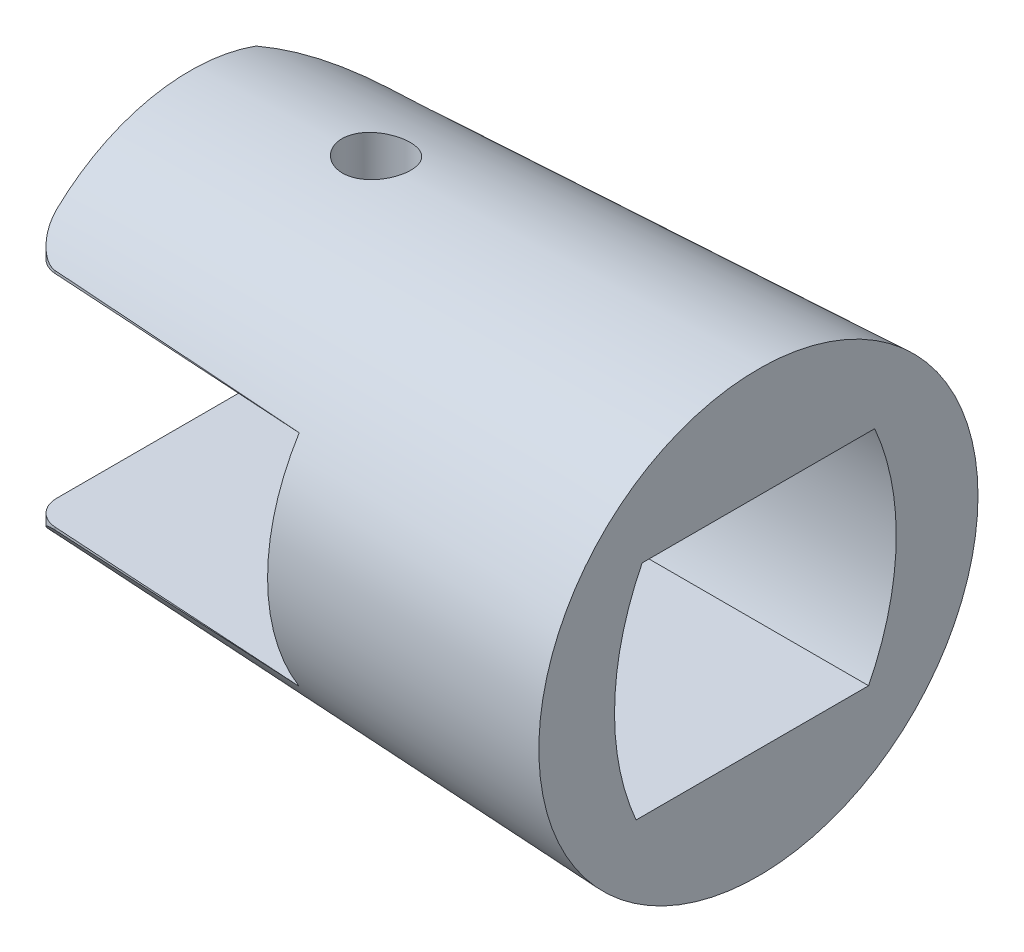
SolidWorks part; units mm, degrees
ref_plane "Ön Düzlem" through (0, 0, 0) normal (0, 0, 1) x (1, 0, 0)
ref_plane "Üst Düzlem" through (0, 0, 0) normal (0, 1, 0) x (1, 0, 0)
ref_plane "Sağ Düzlem" through (0, 0, 0) normal (1, 0, 0) x (0, 0, -1)
sketch "Sketch1" plane through (0, 0, 0) normal (1, 0, 0) x (0, 0, -1)
  circle A0 centre (0, 0) radius 8.5
  dimension "D1" = 17
sketch "Sketch3" plane through (0, 0, 0) normal (0, 1, 0) x (1, 0, 0)
  line L0 (0, 0) -> (-22, 0)
  dimension "D1" = 22
ref_plane "Plane1" through (-22, 0, 0) normal (1, 0, 0) x (0, 0, -1)
sketch "Sketch4" plane through (-22, 0, 0) normal (1, 0, 0) x (0, 0, -1)
  circle A0 centre (0, 0) radius 7.5
loft "Loft1" add profiles "Sketch4", "Sketch1" connector at (-22, 1.76, -7.2906) connector at (0, 2.119, -8.2316)
sketch "Sketch5" plane through (0, 0, 0) normal (0, 0, 1) x (1, 0, 0)
  line L0 (0, 0) -> (-10, 0) construction
  line L1 (0, 0) -> (-22, 0) construction
  line L2 (-11, 4.25) -> (-24.9848, 4.25)
  line L3 (-11, 4.25) -> (-11, -4.25)
  line L4 (-24.9848, 4.25) -> (-24.9848, -4.25)
  line L5 (-24.9848, -4.25) -> (-11, -4.25)
  line L6 (-11, -4.25) -> (-10.9931, -4.2764)
  line L7 (0, -8.5) -> (0, 8.5) construction
  dimension "D1" = 10
  dimension "D2" = 8.5
  dimension "D3" = 4.25
  dimension "D4" = 11
extrude "Cut-Extrude1" cut sketch "Sketch5" against normal blind 10 and the other way blind 10 contours L4 L5 L3 L2 region at (-17.9924, 0, 0)
sketch "Sketch7" plane through (0, 0, 0) normal (0, 1, 0) x (1, 0, 0)
  line L0 (-11, 6.7777) -> (-11, -6.7777)
  line L1 (-11, -6.7777) -> (-23.0023, -6.0429)
  line L2 (-23.0023, -6.0429) -> (-23.0231, -1.4883)
  line L3 (-11, 6.7777) -> (-16.5274, 6.6846)
  line L4 (-11, -6.7777) -> (-11, -8) construction
  line L5 (-11, 6.7777) -> (-11, 10.3705)
  line L6 (-11, 10.3705) -> (-27.9181, 10.3705)
  line L7 (-27.9181, 10.3705) -> (-27.9181, -8.5015)
  line L8 (-27.9181, -8.5015) -> (-11, -8.5015)
  line L9 (-11, -8.5015) -> (-11, -6.7777)
  arc A0 (-16.5274, 6.6846) -> (-23.0231, -1.4883) centre (-14.6815, -1.4502) ccw
  spline S0 degree 3 poles (-11, -6.7777) (-14.6668, -6.581) (-18.3335, -6.3819) (-22, -6.1796) knots 0 0 0 0 1 1 1 1 construction
  spline S1 degree 3 poles (-22, 6.1796) (-18.3335, 6.3819) (-14.6668, 6.581) (-11, 6.7777) knots 0 0 0 0 1 1 1 1 construction
  dimension "D4" = 5.5274
  dimension "D6" = 8.3417
  dimension "D1" = 12.0023
  dimension "D2" = 4.5546
  dimension "D3" = 86.496
  dimension "D5" = 89.035
extrude "Cut-Extrude2" cut sketch "Sketch7" against normal blind 10 and the other way blind 10 contours A0 L3 L5 L6 L7 L8 L9 L1 L2 region at (-13.768, 0, -6.9846)
sketch "Sketch8" plane through (0, 0, 0) normal (0, 1, 0) x (1, 0, 0)
  line L0 (-11, -8) -> (-15.3, -8) construction
  line L1 (-15.3, -8) -> (-15.3, 0.5) construction
  circle A0 centre (-15.3, 0.5) radius 1.25
  dimension "D1" = 4.3
  dimension "D2" = 8.5
extrude "Cut-Extrude3" cut sketch "Sketch8" against normal blind 10 and the other way blind 10
sketch "Sketch9" plane through (0, 0, 0) normal (1, 0, 0) x (0, 0, -1)
  line L0 (5.1446, 4.1876) -> (5.1446, -4.2327)
  line L2 (-3.4805, 4.1876) -> (-3.4805, -4.3677)
  arc A0 (5.1446, 4.1876) -> (-3.4805, 4.1876) centre (0.8321, -5.3223) ccw
  arc A1 (5.1446, -4.2327) -> (-3.4805, -4.3677) centre (0.7011, 4.0719) cw
sketch "Sketch10" plane through (0, 0, 0) normal (1, 0, 0) x (0, 0, -1)
  line L0 (-4.5, 4.25) -> (4.5, 4.25)
  line L1 (-4.7349, -4.25) -> (4.2651, -4.25)
  line L2 (-8.5, 0) -> (8.5, 0) construction
  line L3 (0, -8.5) -> (0, 8.5) construction
  line L4 (0, 8.5) -> (0, 5.4132) construction
  arc A0 (-4.5, 4.25) -> (-4.7349, -4.25) centre (4.4303, -0.25) ccw
  arc A1 (4.5, 4.25) -> (4.2651, -4.25) centre (-4.6652, 0.25) cw
  circle A2 centre (0, 0) radius 8.5 construction
  dimension "D1" = 10
  dimension "D2" = 9
  dimension "D3" = 4.5
  dimension "D4" = 8.5
  dimension "D5" = 4.25
extrude "Cut-Extrude4" cut sketch "Sketch10" against normal blind 12
fillet "Fillet1" radius 1 2 edges
